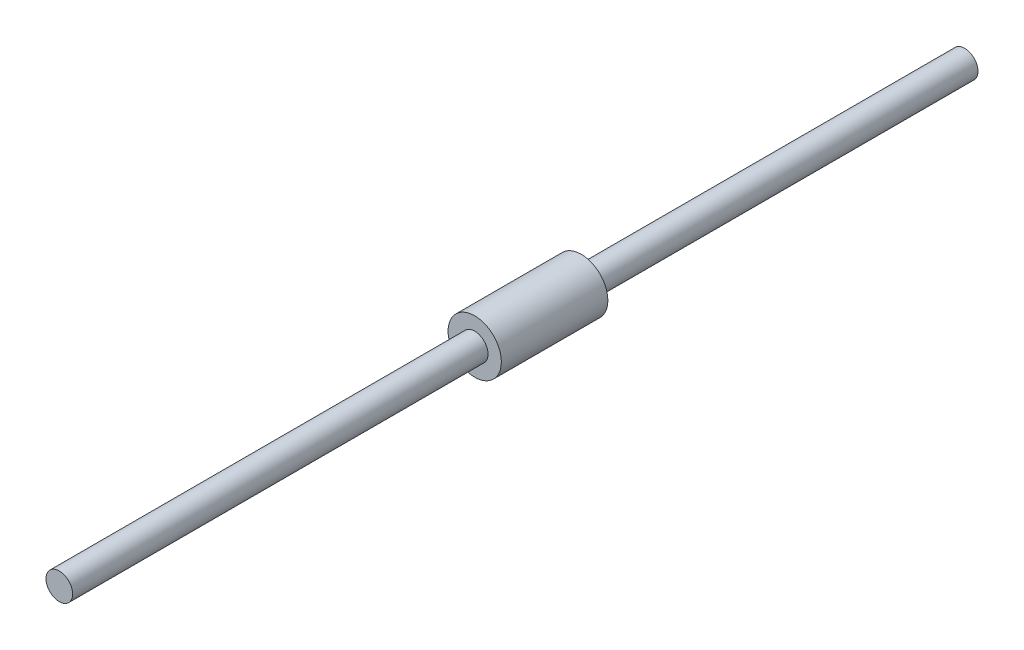
SolidWorks part; units mm, degrees
ref_plane "Front Plane" through (0, 0, 0) normal (0, 0, 1) x (1, 0, 0)
ref_plane "Top Plane" through (0, 0, 0) normal (0, 1, 0) x (1, 0, 0)
ref_plane "Right Plane" through (0, 0, 0) normal (1, 0, 0) x (0, 0, -1)
sketch "Sketch1" plane through (0, 0, 0) normal (0, 0, 1) x (1, 0, 0)
  circle A0 centre (0, 0) radius 12.5
  circle A2 centre (0, 0) radius 25
extrude "Boss-Extrude1" add sketch "Sketch1" along normal blind 50 and the other way blind 50 contours A0 | A2 region at (0, 0, 0)
sketch "Sketch3" plane through (0, 0, 50) normal (0, 0, 1) x (1, 0, 0)
  circle A0 centre (0, 0) radius 12.5
extrude "Boss-Extrude3" add sketch "Sketch3" along normal blind 390 and the other way blind 460
